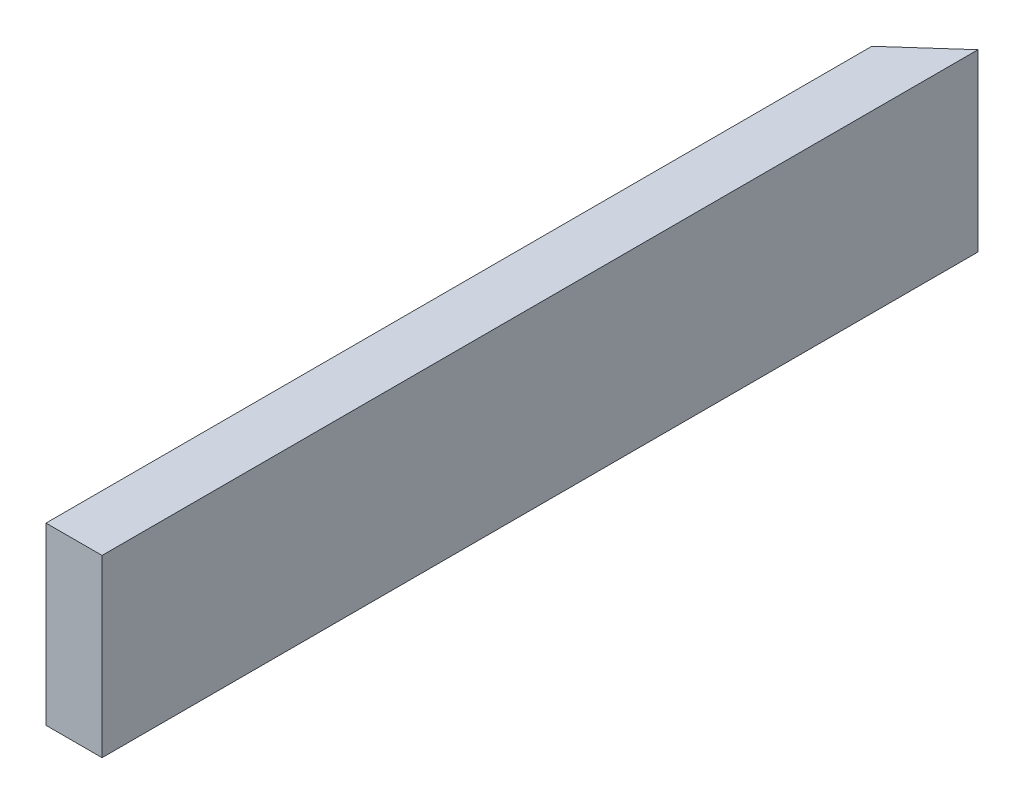
SolidWorks part; units mm, degrees
ref_plane "Front Plane" through (0, 0, 0) normal (0, 0, 1) x (1, 0, 0)
ref_plane "Top Plane" through (0, 0, 0) normal (0, 1, 0) x (1, 0, 0)
ref_plane "Right Plane" through (0, 0, 0) normal (1, 0, 0) x (0, 0, -1)
sketch "Sketch1" plane through (0, 0, 0) normal (0, 0, 1) x (1, 0, 0)
  line L1 (-4.1032, 12.8387) -> (-0.9032, 12.8387)
  line L2 (-4.1032, 12.8387) -> (-4.1032, 2.8387)
  line L3 (-4.1032, 2.8387) -> (-0.9032, 2.8387)
  line L4 (-0.9032, 12.8387) -> (-0.9032, 2.8387)
  dimension "D1" = 3.2
  dimension "D2" = 10
extrude "Boss-Extrude1" add sketch "Sketch1" along normal blind 50
ref_plane "Plane1" through (0, 12.8387, 0) normal (0, 1, 0) x (1, 0, 0)
sketch "Sketch3" plane through (0, 12.8387, 0) normal (0, 1, 0) x (1, 0, 0)
  line L0 (-0.9032, 0) -> (-4.1032, -2.8611)
  line L1 (-4.1032, -50) -> (-4.1032, 0) construction
  line L2 (-4.1032, -2.8611) -> (-4.1032, 0)
  line L3 (-4.1032, 0) -> (-0.9032, 0)
  dimension "D1" = 41.8
extrude "Cut-Extrude1" cut sketch "Sketch3" against normal blind 52
